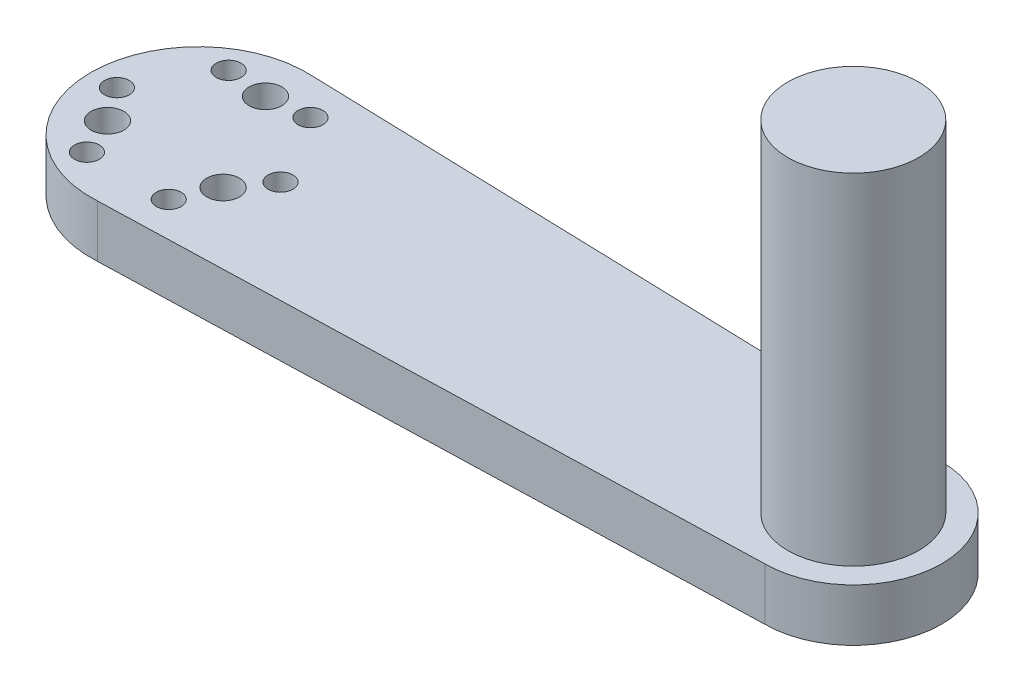
SolidWorks part; units mm, degrees
ref_plane "前视基准面" through (0, 0, 0) normal (0, 0, 1) x (1, 0, 0)
ref_plane "上视基准面" through (0, 0, 0) normal (0, 1, 0) x (1, 0, 0)
ref_plane "右视基准面" through (0, 0, 0) normal (1, 0, 0) x (0, 0, -1)
other "Configuration Table"
sketch "草图1" plane through (0, 0, 0) normal (0, 1, 0) x (1, 0, 0)
  line L0 (0, 0) -> (0, 12.5) construction
  line L1 (0, 0) -> (0, -12.5) construction
  line L2 (0, 0) -> (-6.25, 10.8253)
  line L3 (0, 0) -> (100, 0)
  line L4 (100, -13.5) -> (0, -16.5)
  line L5 (100, 13.5) -> (0, 16.5)
  circle A0 centre (0, 0) radius 10.2
  circle A1 centre (0, 0) radius 12.5
  circle A4 centre (0, 0) radius 16.5
  circle A7 centre (100, 0) radius 13.5
  circle A8 centre (100, 0) radius 10
  dimension "D1" = 20.4
  dimension "D2" = 25
  dimension "D3" = 100
  dimension "D4" = 30
  dimension "D5" = 33
  dimension "D6" = 27
  dimension "D7" = 20
extrude "凸台-拉伸1" add sketch "草图1" along normal blind 8 contours A4
sketch "草图4" plane through (0, 8, 0) normal (0, 1, 0) x (1, 0, 0)
  line L0 (0, -10.2) -> (0, 10.2) construction
  line L1 (0, 0) -> (-6.25, 10.8253)
  circle A0 centre (0, 0) radius 10.2
  circle A1 centre (0, 0) radius 12.5
  circle A2 centre (0, 10.2) radius 2.5
  circle A3 centre (-6.25, 10.8253) radius 1.9
  circle A4 centre (6.25, 10.8253) radius 1.9
  circle A5 centre (12.5, 0) radius 1.9
  circle A6 centre (6.25, -10.8253) radius 1.9
  circle A7 centre (-6.25, -10.8253) radius 1.9
  circle A8 centre (-12.5, 0) radius 1.9
  circle A9 centre (8.8335, -5.1) radius 2.5
  circle A10 centre (-8.8335, -5.1) radius 2.5
  point P23 (0, 0)
  point P28 (0, 0)
  dimension "D1" = 20.4
  dimension "D2" = 25
  dimension "D4" = 3.8
  dimension "D5" = 5
  dimension "D3" = 30
  dimension "D6" = 6
  dimension "D7" = 3
extrude "切除-拉伸1" cut sketch "草图4" against normal through all and the other way through all contours A8 | A3 | A2 | A10 | A7 | A6 | A9 | A5 | A4
extrude "凸台-拉伸2" add sketch "草图1<3>" along normal blind 8 contours A7 L3 A4 L4 | A7 L5 A4 L3 | A8 A7 region at (50.3121, 0, -7.8476) region at (50.3121, 0, 7.8476) region at (90.7241, 0, -9.2759)
sketch "草图1<3>" plane through (0, 0, 0) normal (0, 1, 0) x (1, 0, 0) same geometry as "草图1"
extrude "凸台-拉伸3" add sketch "草图1<4>" along normal blind 60 contours A8 region at (100, 0, -9.7172)
sketch "草图1<4>" plane through (0, 0, 0) normal (0, 1, 0) x (1, 0, 0) same geometry as "草图1"
